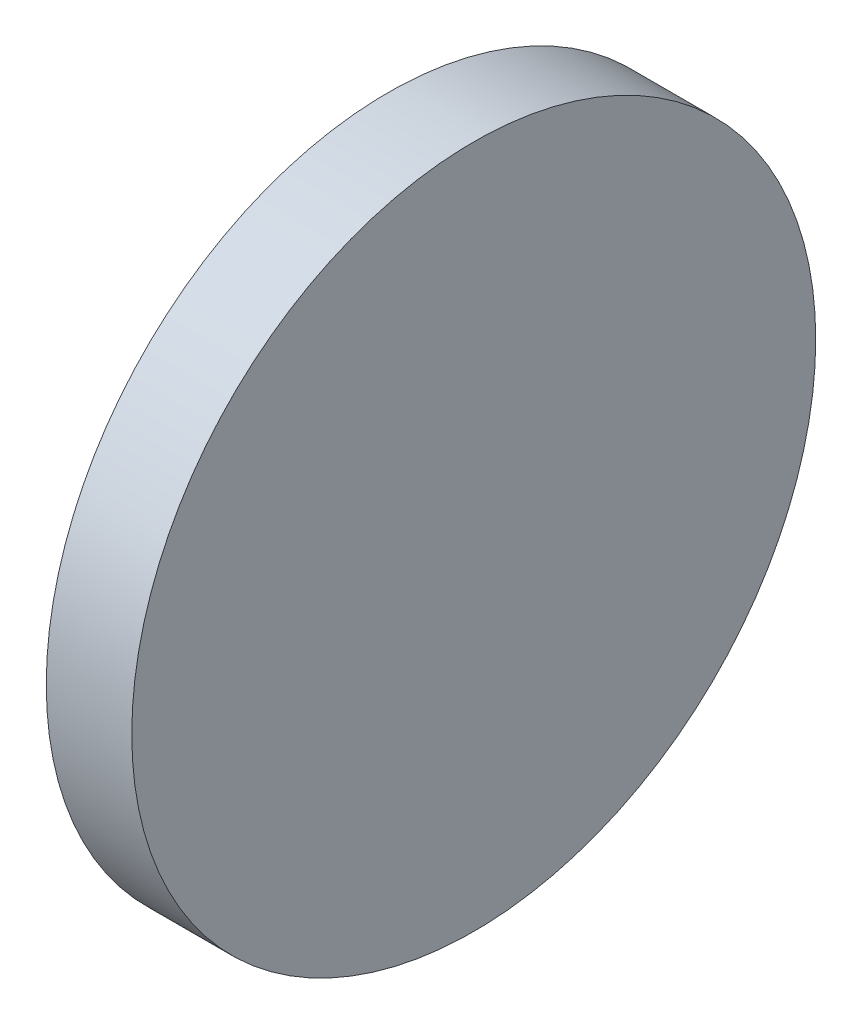
SolidWorks part; units mm, degrees
ref_plane "Plan de face" through (0, 0, 0) normal (1, 0, 0) x (0, 1, 0)
ref_plane "Plan de dessus" through (0, 0, 0) normal (0, 0, 1) x (0, 1, 0)
ref_plane "Plan de droite" through (0, 0, 0) normal (0, 1, 0) x (-1, 0, 0)
sketch "Esquisse1" plane through (0, 0, 0) normal (1, 0, 0) x (0, 1, 0)
  circle A0 centre (0, 0) radius 40
  circle A1 centre (0, 32) radius 5.5
  circle A2 centre (12.2459, 29.5641) radius 5.5
  circle A3 centre (22.6274, 22.6274) radius 5.5
  circle A4 centre (29.5641, 12.2459) radius 5.5
  circle A5 centre (32, 0) radius 5.5
  circle A6 centre (29.5641, -12.2459) radius 5.5
  circle A7 centre (22.6274, -22.6274) radius 5.5
  circle A8 centre (12.2459, -29.5641) radius 5.5
  circle A9 centre (0, -32) radius 5.5
  circle A10 centre (-12.2459, -29.5641) radius 5.5
  circle A11 centre (-22.6274, -22.6274) radius 5.5
  circle A12 centre (-29.5641, -12.2459) radius 5.5
  circle A13 centre (-32, 0) radius 5.5
  circle A14 centre (-29.5641, 12.2459) radius 5.5
  circle A15 centre (-22.6274, 22.6274) radius 5.5
  circle A16 centre (-12.2459, 29.5641) radius 5.5
  circle A17 centre (-11.4293, 17.1051) radius 5.5
  circle A18 centre (4.0134, 20.1768) radius 5.5
  circle A19 centre (17.1051, 11.4293) radius 5.5
  circle A20 centre (20.1768, -4.0134) radius 5.5
  circle A21 centre (11.4293, -17.1051) radius 5.5
  circle A22 centre (-4.0134, -20.1768) radius 5.5
  circle A23 centre (-17.1051, -11.4293) radius 5.5
  circle A24 centre (-20.1768, 4.0134) radius 5.5
  circle A25 centre (5.5277, 8.2728) radius 5.5
  circle A26 centre (8.2728, -5.5277) radius 5.5
  circle A27 centre (-5.5277, -8.2728) radius 5.5
  circle A28 centre (-8.2728, 5.5277) radius 5.5
  point P37 (0, 0)
  point P54 (0, 0)
  point P64 (0, 0)
  dimension "D1" = 80
  dimension "D2" = 11
  dimension "D5" = 11
  dimension "D9" = 11
  dimension "D3" = 32
  dimension "D6" = 12.4858
  dimension "D7" = 12.4858
  dimension "D10" = 12
  dimension "D11" = 12
  dimension "D4" = 16
  dimension "D8" = 8
  dimension "D12" = 4
extrude "Boss.-Extru.1" add sketch "Esquisse1" along normal blind 10
sketch "Esquisse2" plane through (10, 0, 0) normal (1, 0, 0) x (0, 1, 0)
  circle A0 centre (0, 0) radius 40
extrude "Boss.-Extru.2" add sketch "Esquisse2" against normal blind 8
